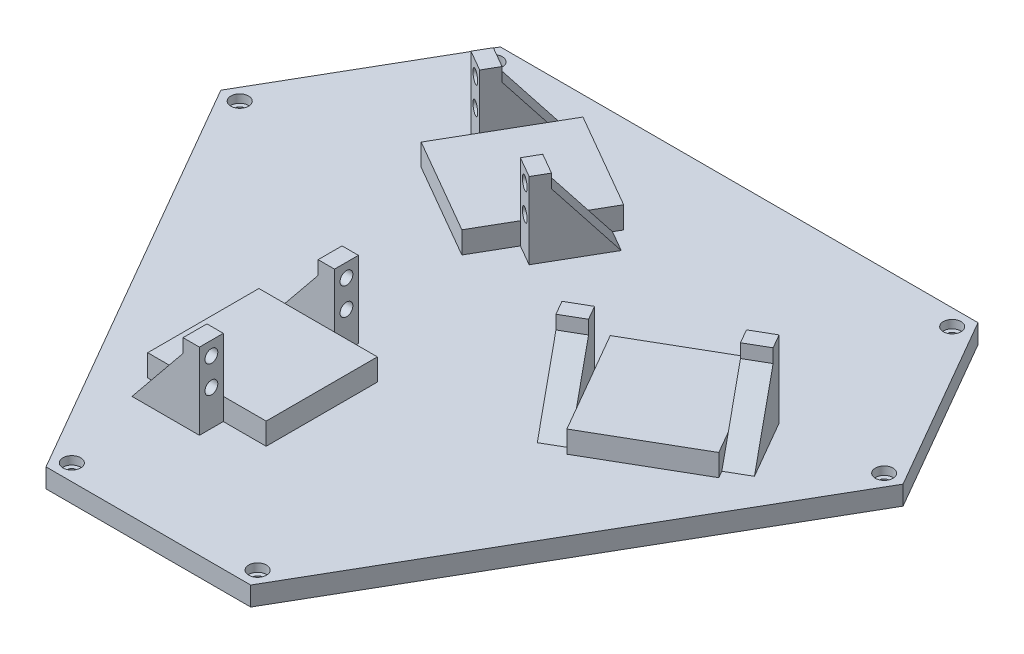
SolidWorks part; units mm, degrees
ref_plane "Front Plane" through (0, 0, 0) normal (0, 0, 1) x (1, 0, 0)
ref_plane "Top Plane" through (0, 0, 0) normal (0, 1, 0) x (1, 0, 0)
ref_plane "Right Plane" through (0, 0, 0) normal (1, 0, 0) x (0, 0, -1)
sketch "Sketch1" plane through (0, 0, 0) normal (0, 1, 0) x (1, 0, 0)
  line L14 (-106.25, 184.0304) -> (81.25, 75.7772) construction
  line L15 (87.5, 216.5064) -> (-87.5, 216.5064)
  line L16 (-87.5, 216.5064) -> (-125, 151.5544)
  line L17 (-125, 151.5544) -> (-37.5, 0)
  line L18 (-37.5, 0) -> (37.5, 0)
  line L19 (37.5, 0) -> (125, 151.5544)
  line L20 (125, 151.5544) -> (87.5, 216.5064)
  line L21 (106.25, 184.0304) -> (-81.25, 75.7772) construction
  line L22 (0, 216.5064) -> (0, 0) construction
  line L23 (87.5, 216.5064) -> (-37.5, 0) construction
  line L24 (-87.5, 216.5064) -> (37.5, 0) construction
  line L25 (125, 151.5544) -> (-125, 151.5544) construction
  point P1 (0, 216.5064)
  point P8 (0, 122.6869)
  dimension "D1" = 175
  dimension "D2" = 75
  dimension "D3" = 120
extrude "Boss-Extrude1" add sketch "Sketch1" along normal blind 7
sketch "Sketch2" plane through (0, 7, 0) normal (0, 1, 0) x (1, 0, 0)
  line L4 (86.7128, 124.1521) -> (75.3628, 143.8109) construction
  line L5 (89.2128, 119.822) -> (53.9222, 99.447) construction
  line L6 (-42.1253, 201.3799) -> (-6.8347, 181.0049) construction
  line L8 (-42.1253, 201.3799) -> (-44.6253, 197.0498) construction
  line L9 (81.3167, 147.2484) -> (34.1183, 119.9984) construction
  line L10 (-47.0875, 46.8589) -> (-42.0875, 46.8589) construction
  line L12 (-47.0875, 46.8589) -> (-47.0875, 87.6089) construction
  line L13 (-19.3875, 39.9839) -> (-19.3875, 94.4839) construction
  line L14 (-3.6875, 87.6089) -> (-3.6875, 46.8589) construction
  line L15 (-61.9292, 180.8285) -> (-14.7308, 153.5785) construction
  line L16 (-28.5347, 143.4194) -> (-6.8347, 181.0049)
  line L17 (-28.5347, 143.4194) -> (-63.8253, 163.7944)
  line L18 (-6.8347, 181.0049) -> (-42.1253, 201.3799)
  line L19 (-63.8253, 163.7944) -> (-42.1253, 201.3799)
  line L21 (-3.6875, 87.6089) -> (-47.0875, 87.6089)
  line L22 (-3.6875, 87.6089) -> (-3.6875, 46.8589)
  line L23 (-47.0875, 87.6089) -> (-47.0875, 46.8589)
  line L24 (-3.6875, 46.8589) -> (-47.0875, 46.8589)
  line L26 (32.2222, 137.0325) -> (53.9222, 99.447)
  line L27 (32.2222, 137.0325) -> (67.5128, 157.4075)
  line L28 (53.9222, 99.447) -> (89.2128, 119.822)
  line L29 (67.5128, 157.4075) -> (89.2128, 119.822)
  line L31 (-55.9753, 177.391) -> (-63.553, 181.766)
  line L32 (-55.9753, 177.391) -> (-52.9753, 182.5872)
  line L33 (-63.553, 181.766) -> (-60.553, 186.9622)
  line L34 (-52.9753, 182.5872) -> (-60.553, 186.9622)
  line L35 (-20.6847, 157.016) -> (-13.107, 152.641)
  line L36 (-20.6847, 157.016) -> (-17.6847, 162.2122)
  line L37 (-13.107, 152.641) -> (-10.107, 157.8372)
  line L38 (-17.6847, 162.2122) -> (-10.107, 157.8372)
  line L39 (82.9405, 148.1859) -> (75.3628, 143.8109)
  line L40 (82.9405, 148.1859) -> (85.9405, 142.9897)
  line L41 (75.3628, 143.8109) -> (78.3628, 138.6147)
  line L42 (85.9405, 142.9897) -> (78.3628, 138.6147)
  line L43 (32.4945, 119.0609) -> (40.0722, 123.4359)
  line L44 (32.4945, 119.0609) -> (35.4945, 113.8647)
  line L45 (40.0722, 123.4359) -> (43.0722, 118.2397)
  line L46 (35.4945, 113.8647) -> (43.0722, 118.2397)
  line L47 (-19.3875, 96.3589) -> (-19.3875, 87.6089)
  line L48 (-19.3875, 96.3589) -> (-25.3875, 96.3589)
  line L49 (-19.3875, 87.6089) -> (-25.3875, 87.6089)
  line L50 (-25.3875, 96.3589) -> (-25.3875, 87.6089)
  line L51 (-19.3875, 46.8589) -> (-19.3875, 38.1089)
  line L52 (-19.3875, 46.8589) -> (-25.3875, 46.8589)
  line L53 (-19.3875, 38.1089) -> (-25.3875, 38.1089)
  line L54 (-25.3875, 46.8589) -> (-25.3875, 38.1089)
  point P0 (-48.7763, 183.0246)
  dimension "D1" = 6
  dimension "D2" = 8.75
extrude "Boss-Extrude2" add sketch "Sketch2" along normal blind 8 contours L19 L17 L16 L18 | L24 L22 L21 L23 | L29 L27 L26 L28 region at (-35.33, 7, -172.3997) region at (-25.3875, 7, -67.2339) region at (60.7175, 7, -128.4272)
extrude "Boss-Extrude3" add sketch "Sketch2<3>" along normal blind 28 contours L19 L34 L33 L31 | L38 L16 L35 L37 | L48 L50 L21 L47 | L24 L54 L53 L51 | L44 L46 L26 L43 | L42 L40 L39 L29 region at (-15.3959, 7, -157.4266) region at (-58.2641, 7, -182.1766) region at (-22.3875, 7, -91.9839) region at (-22.3875, 7, -42.4839) region at (37.7834, 7, -118.6503) region at (80.6516, 7, -143.4003)
sketch "Sketch2<3>" plane through (0, 7, 0) normal (0, 1, 0) x (1, 0, 0) same geometry as "Sketch2"
sketch "Sketch3" plane through (-43.4313, 0, -75.2251) normal (-0.5, 0, -0.866) x (-0.866, 0, 0.5)
  circle A0 centre (-141.5465, 20) radius 2.35
  circle A1 centre (-141.5465, 30) radius 2.35
  circle A2 centre (-92.0465, 30) radius 2.35
  circle A3 centre (-92.0465, 20) radius 2.35
  arc A4 (-89.5965, 20.7925) -> (-89.5965, 19.2075) centre (-92.0465, 20) ccw construction
  point P11 (-94.052, 20.7587)
  dimension "D1" = 4.7
extrude "Cut-Extrude1" cut sketch "Sketch3" against normal blind 4
sketch "Sketch4" plane through (62.8187, 0, -108.8053) normal (-0.5, 0, 0.866) x (0.866, 0, 0.5)
  circle A0 centre (-141.5465, 30) radius 2.35
  circle A1 centre (-92.0465, 20) radius 2.35
  circle A2 centre (-92.0465, 30) radius 2.35
  circle A3 centre (-141.5465, 20) radius 2.35
  dimension "D1" = 4.7
extrude "Cut-Extrude2" cut sketch "Sketch4" against normal blind 4
sketch "Sketch6" plane through (-19.3875, 0, 0) normal (1, 0, 0) x (0, 0, -1)
  circle A0 centre (42.4839, 30) radius 2.35
  circle A1 centre (91.9839, 20) radius 2.35
  circle A2 centre (91.9839, 30) radius 2.35
  circle A3 centre (42.4839, 20) radius 2.35
  dimension "D1" = 4.7
extrude "Cut-Extrude6" cut sketch "Sketch6" against normal blind 4
hole_wizard "CBORE for M3 SHCS1" positions "Sketch8" profile "Sketch9" counterbore size "M3" standard "ANSI Metric" end condition up to next
sketch "Sketch8" plane through (0, 7, 0) normal (0, 1, 0) x (1, 0, 0)
  line L23 (118.0718, 151.5544) -> (84.0359, 210.5064)
  line L24 (84.0359, 210.5064) -> (-84.0359, 210.5064)
  line L25 (-84.0359, 210.5064) -> (-118.0718, 151.5544)
  line L26 (-118.0718, 151.5544) -> (-34.0359, 6)
  line L27 (-34.0359, 6) -> (34.0359, 6)
  line L28 (34.0359, 6) -> (118.0718, 151.5544)
  line L29 (118.0718, 151.5544) -> (84.0359, 210.5064) construction
  line L30 (84.0359, 210.5064) -> (-84.0359, 210.5064) construction
  line L31 (-84.0359, 210.5064) -> (-118.0718, 151.5544) construction
  line L32 (-118.0718, 151.5544) -> (-34.0359, 6) construction
  line L33 (-34.0359, 6) -> (34.0359, 6) construction
  line L34 (34.0359, 6) -> (118.0718, 151.5544) construction
  point P0 (-84.0359, 210.5064)
  point P2 (84.0359, 210.5064)
  point P4 (118.0718, 151.5544)
  point P6 (34.0359, 6)
  point P8 (-34.0359, 6)
  point P10 (-118.0718, 151.5544)
  point P63 (-81.1705, 212.9065)
  point P64 (0, 0)
  point P65 (0, 0)
  point P66 (0, 0)
  point P67 (0, 0)
  point P68 (0, 0)
  point P69 (0, 0)
  dimension "D1" = 6
sketch "Sketch9" plane through (-84.0359, 7, -210.5064) normal (1, 0, 0) x (0, 0, 1)
  line L0 (0, 0) -> (0, 7)
  line L1 (0, 7) -> (1.7, 7)
  line L3 (1.7, 7) -> (1.7, 3)
  line L4 (1.7, 3) -> (3.25, 3)
  line L5 (3.25, 3) -> (3.25, 0)
  line L7 (3.25, 0) -> (0, 0)
  line L11 (0, -6.35) -> (0, 107.95) construction
  dimension "Thru Hole Dia." = 3.4
  dimension "Thru Hole Depth" = 7
  dimension "C'Bore Dia." = 6.5
  dimension "C'Bore Depth" = 3
ref_plane "Plane2" through (0, 0, -42.4839) normal (0, 0, 1) x (1, 0, 0)
sketch "Sketch12" plane through (0, 0, -42.4839) normal (0, 0, 1) x (1, 0, 0)
  line L0 (-25.3875, 30) -> (-44.0875, 7)
  line L1 (-25.3875, 35) -> (-25.3875, 7) construction
  line L2 (-25.3875, 7) -> (-47.0875, 7) construction
  line L4 (-19.3875, 35) -> (-25.3875, 35) construction
  dimension "D1" = 5
  dimension "D2" = 3
rib "Rib1" sketch "Sketch12" sketch "Sketch12" thickness 8.75 extrusion direction parallel to sketch draft on no parameters "D1"=8.75
ref_plane "Plane3" through (0, 0, -91.9839) normal (0, 0, 1) x (1, 0, 0)
sketch "Sketch13" plane through (0, 0, -91.9839) normal (0, 0, 1) x (1, 0, 0)
  line L0 (-25.3875, 30) -> (-44.0875, 7)
  line L1 (37.5, 7) -> (125, 7) construction
  line L2 (-25.3875, 15) -> (-25.3875, 7) construction
  point P2 (-45.9562, 6.1462)
  point P3 (-44.0875, 0.6156)
  point P6 (0, 0)
  point P9 (-29.8701, 30)
  point P10 (0, 0)
  dimension "D1" = 5
  dimension "D2" = 3
rib "Rib4" sketch "Sketch13" sketch "Sketch13" thickness 8.75 extrusion direction parallel to sketch draft on no parameters "D1"=8.75
ref_plane "Plane4" through (-122.5829, 0, -70.7733) normal (-0.866, 0, -0.5) x (-0.5, 0, 0.866)
sketch "Sketch14" plane through (-122.5829, 0, -70.7733) normal (-0.866, 0, -0.5) x (-0.5, 0, 0.866)
  line L0 (-131.6375, 30) -> (-150.3375, 7)
  line L1 (-131.6375, 35) -> (-131.6375, 7) construction
  line L2 (-131.6375, 7) -> (-153.3375, 7) construction
  line L3 (-153.3375, 15) -> (-153.3375, 7) construction
  dimension "D1" = 5
  dimension "D2" = 3
rib "Rib5" sketch "Sketch14" sketch "Sketch14" thickness 8.75 extrusion direction parallel to sketch draft on no parameters "D1"=8.75
ref_plane "Plane5" through (-79.7146, 0, -46.0233) normal (-0.866, 0, -0.5) x (-0.5, 0, 0.866)
sketch "Sketch15" plane through (-79.7146, 0, -46.0233) normal (-0.866, 0, -0.5) x (-0.5, 0, 0.866)
  line L0 (-131.6375, 30) -> (-150.3375, 7)
  line L1 (-131.6375, 35) -> (-131.6375, 30) construction
  line L2 (-150.3375, 7) -> (-153.3375, 7) construction
  line L3 (-125.6375, 35) -> (-131.6375, 35) construction
  dimension "D1" = 5
  dimension "D2" = 3
rib "Rib6" sketch "Sketch15" sketch "Sketch15" thickness 8.75 extrusion direction parallel to sketch draft on no parameters "D1"=8.75
ref_plane "Plane6" through (122.5829, 0, -70.7733) normal (0.866, 0, -0.5) x (-0.5, 0, -0.866)
sketch "Sketch16" plane through (122.5829, 0, -70.7733) normal (0.866, 0, -0.5) x (-0.5, 0, -0.866)
  line L0 (80.8625, 30) -> (62.1625, 7)
  line L1 (80.8625, 35) -> (80.8625, 7) construction
  line L2 (80.8625, 7) -> (59.1625, 7) construction
  line L3 (86.8625, 35) -> (80.8625, 35) construction
  line L4 (59.1625, 15) -> (59.1625, 7) construction
  dimension "D1" = 5
  dimension "D2" = 3
rib "Rib7" sketch "Sketch16" sketch "Sketch16" thickness 8.75 extrusion direction parallel to sketch draft on no parameters "D1"=8.75
ref_plane "Plane7" through (79.7146, 0, -46.0233) normal (0.866, 0, -0.5) x (-0.5, 0, -0.866)
sketch "Sketch17" plane through (79.7146, 0, -46.0233) normal (0.866, 0, -0.5) x (-0.5, 0, -0.866)
  line L0 (80.8625, 30) -> (62.1625, 7)
  line L1 (80.8625, 35) -> (80.8625, 30) construction
  line L2 (-18.75, 7) -> (68.75, 7) construction
  line L3 (86.8625, 35) -> (80.8625, 35) construction
  line L4 (59.1625, 15) -> (59.1625, 7) construction
  dimension "D1" = 5
  dimension "D2" = 3
rib "Rib8" sketch "Sketch17" sketch "Sketch17" thickness 8.75 extrusion direction parallel to sketch draft on no parameters "D1"=8.75
